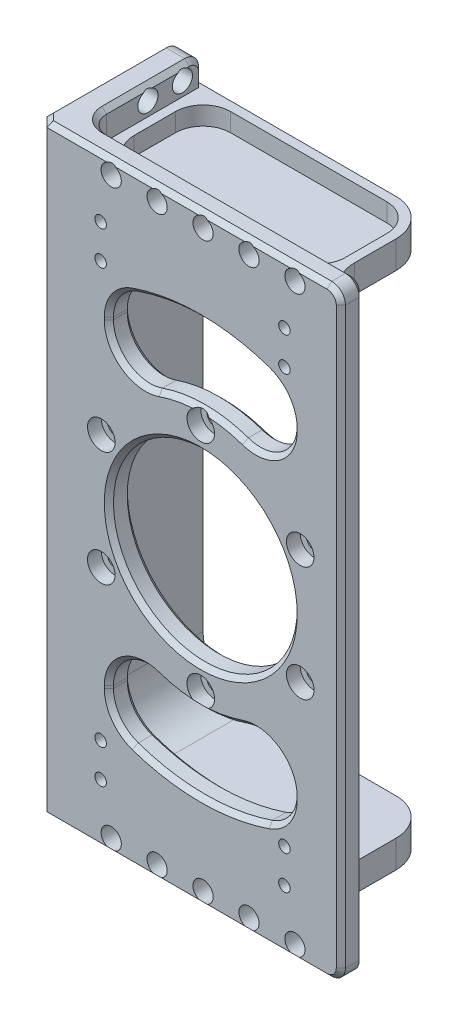
SolidWorks part; units mm, degrees
material "6061 合金"
ref_plane "前视基准面" through (0, 0, 0) normal (0, 0, 1) x (1, 0, 0)
ref_plane "上视基准面" through (0, 0, 0) normal (0, 1, 0) x (1, 0, 0)
ref_plane "右视基准面" through (0, 0, 0) normal (1, 0, 0) x (0, 0, -1)
sketch "草图1" plane through (0, 0, 0) normal (0, 0, 1) x (1, 0, 0)
  line L0 (-237.1759, 120) -> (-237.1759, 1) construction
  line L1 (-237.1759, 60.5) -> (-177.1759, 60.5) construction
  line L2 (812.8241, 60.5) -> (-387.1759, 60.5) construction
  line L3 (-165.4601, -5) -> (-232.1759, -5) construction
  line L4 (-237.1759, 126) -> (-177.1759, 126)
  line L5 (-237.1759, 126) -> (-237.1759, -5)
  line L6 (-237.1759, -5) -> (-177.1759, -5)
  line L7 (-177.1759, 126) -> (-177.1759, -5)
extrude "凸台-拉伸1" add sketch "草图1" along normal blind 5
sketch "草图2" plane through (-237.1759, 0, 0) normal (-1, 0, 0) x (0, 0, 1)
  line L0 (-235, 126) -> (-5, 126) construction
  line L1 (5, -5) -> (-25, -5)
  line L2 (5, -5) -> (5, 126)
  line L3 (5, 126) -> (-25, 126)
  line L4 (-25, -5) -> (-25, 126)
extrude "凸台-拉伸2" add sketch "草图2" along normal blind 6
sketch "草图3" plane through (0, 0, 5) normal (0, 0, 1) x (1, 0, 0)
  line L2 (-236.1759, 60.5) -> (-179.1759, 60.5) construction
  circle A2 centre (-207.6759, 60.5) radius 28.5 construction
  circle A3 centre (-207.6759, 60.5) radius 25 construction
  circle A4 centre (-207.6759, 60.5) radius 20
  dimension "D1" = 5
extrude "切除-拉伸1" cut sketch "草图3" against normal blind 10
sketch "草图4" plane through (0, 0, 5) normal (0, 0, 1) x (1, 0, 0)
  line L4 (-177.1759, 126) -> (-243.1759, 126)
  line L5 (-243.1759, 126) -> (-243.1759, -5)
  line L6 (-243.1759, -5) -> (-177.1759, -5)
  line L7 (-177.1759, -5) -> (-177.1759, 126)
  line L8 (-177.1759, 126) -> (-243.1759, 126)
  line L9 (-243.1759, 126) -> (-243.1759, -5)
  line L10 (-243.1759, -5) -> (-177.1759, -5)
  line L11 (-177.1759, -5) -> (-177.1759, 126)
  circle A0 centre (-207.6759, 60.5) radius 20 construction
  circle A1 centre (-207.6759, 60.5) radius 20
  dimension "D1" = 0
chamfer "倒角1" distance 2 angle 45 1 edges at (-243.1759, 60.5, 5)
fillet "圆角1" radius 3 4 edges at (-240.1759, 126, -25) (-177.1759, 126, 2.5) (-177.1759, -5, 2.5) (-240.1759, -5, -25)
sketch "草图5" plane through (0, 0, 5) normal (0, 0, 1) x (1, 0, 0)
  circle A0 centre (-207.6759, 60.5) radius 25 construction
  point P3 (-207.6759, 85.5)
  point P4 (-186.0252, 73)
  point P7 (-186.0252, 48)
  point P8 (-207.6759, 35.5)
  point P9 (-229.3265, 48)
  point P10 (-229.3265, 73)
  point P11 (-207.6759, 60.5)
  dimension "D1" = 6
sketch "草图13" plane through (0, 0, 5) normal (0, 0, 1) x (1, 0, 0)
  circle A0 centre (-207.6759, 85.5) radius 1.6
  circle A1 centre (-229.3265, 73) radius 1.6
  circle A2 centre (-186.0252, 73) radius 1.6
  circle A3 centre (-186.0252, 48) radius 1.6
  circle A4 centre (-207.6759, 35.5) radius 1.6
  circle A5 centre (-229.3265, 48) radius 1.6
extrude "切除-拉伸2" cut sketch "草图13" against normal blind 6
sketch "草图14" plane through (0, 0, 5) normal (0, 0, 1) x (1, 0, 0)
  circle A0 centre (-207.6759, 85.5) radius 3
  circle A1 centre (-186.0252, 73) radius 3
  circle A2 centre (-186.0252, 48) radius 3
  circle A3 centre (-207.6759, 35.5) radius 3
  circle A4 centre (-229.3265, 48) radius 3
  circle A5 centre (-229.3265, 73) radius 3
extrude "切除-拉伸3" cut sketch "草图14" against normal blind 3
chamfer "倒角4" distance 1 angle 45 12 edges at (-242.1759, -5, 4) (-210.6759, -5, 5) (-243.1759, -5, -9.5) (-178.0545, -4.1213, 5) (-243.1759, -4.1213, -24.1213) (-177.1759, 60.5, 5) (-243.1759, 60.5, -25) (-178.0545, 125.1213, 5) (-243.1759, 125.1213, -24.1213) (-210.6759, 126, 5) (-242.1759, 126, 4) (-243.1759, 126, -9.5)
sketch "草图15" plane through (0, 0, 0) normal (0, -1, 0) x (1, 0, 0)
  line L0 (-11.5, -120) -> (-5.5, -120) construction
  line L1 (-11.5, -191) -> (-11.5, -49) construction
  line L2 (-5.5, -108) -> (-5.5, -132) construction
  line L3 (-8.5, -100) -> (-8.5, -140) construction
  line L4 (-8.5, -80) -> (-8.5, -160) construction
  line L5 (-8.5, -60) -> (-8.5, -180) construction
  point P9 (-8.5, -120)
  point P13 (-8.5, -120)
  point P16 (-8.5, -120)
sketch "草图16" plane through (0, 0, 0) normal (0, 0, -1) x (-1, 0, 0)
  line L5 (237.1759, 126) -> (237.1759, 120) construction
  line L6 (237.1759, 123) -> (237.1759, -2) construction
  line L8 (237.1759, 120) -> (187.1759, 120)
  line L9 (237.1759, 120) -> (237.1759, 114)
  line L10 (237.1759, 114) -> (187.1759, 114)
  line L11 (187.1759, 120) -> (187.1759, 114)
extrude "凸台-拉伸4" add sketch "草图16" along normal up to surface (25 mm away) up to face at (-239.6759, 60.5, -25)
ref_plane "基准面1" through (0, 60.5, 0) normal (0, -1, 0) x (-1, 0, 0)
mirror "镜向1" about plane through (0, 60.5, 0) normal (0, -1, 0) of "凸台-拉伸4"
fillet "圆角3" radius 4 2 edges at (-237.1759, -2, 0) (-237.1759, 123, 0)
fillet "圆角4" radius 10 2 edges at (-237.1759, 114, -12.5) (-237.1759, 7, -12.5)
fillet "圆角5" radius 8 4 edges at (-187.1759, 117, 0) (-187.1759, 117, -25) (-187.1759, 4, 0) (-187.1759, 4, -25)
sketch "草图17" plane through (0, 120, 0) normal (0, 1, 0) x (1, 0, 0)
  line L4 (-235.1759, 4) -> (-235.1759, 2)
  line L5 (-235.1759, 2) -> (-233.1759, 2)
  line L8 (-189.1759, 8) -> (-189.1759, 17)
  line L9 (-195.1759, 23) -> (-235.1759, 23)
  line L10 (-235.1759, 23) -> (-235.1759, 4)
  line L11 (-233.1759, 2) -> (-187.1759, 2)
  line L12 (-189.1759, 8) -> (-189.1759, 17)
  line L13 (-195.1759, 23) -> (-235.1759, 23)
  line L14 (-235.1759, 23) -> (-235.1759, 4)
  line L15 (-233.1759, 2) -> (-187.1759, 2)
  arc A6 (-189.1759, 17) -> (-195.1759, 23) centre (-195.1759, 17) ccw
  arc A7 (-235.1759, 4) -> (-233.1759, 2) centre (-233.1759, 4) ccw
  arc A8 (-189.1759, 8) -> (-187.1759, 2) centre (-179.1759, 8) ccw
  arc A9 (-189.1759, 17) -> (-195.1759, 23) centre (-195.1759, 17) ccw
  arc A11 (-189.1759, 8) -> (-187.1759, 2) centre (-179.1759, 8) ccw
  dimension "D1" = 2
extrude "切除-拉伸4" cut sketch "草图17" against normal blind 4
mirror "镜向2" about plane through (0, 60.5, 0) normal (0, -1, 0) of "切除-拉伸4"
fillet "圆角6" radius 6 6 edges at (-187.1759, 118, -2) (-235.1759, 118, -23) (-235.1759, 118, -2) (-235.1759, 3, -23) (-187.1759, 3, -2) (-235.1759, 3, -2)
sketch "草图19" plane through (0, 0, 5) normal (0, 0, 1) x (1, 0, 0)
  line L0 (-243.1759, -5) -> (-237.1759, -5) construction
  line L1 (-243.1759, -5) -> (-177.1759, -5) construction
  line L2 (-237.1759, -5) -> (-177.1759, -5) construction
  line L3 (-207.1759, -5) -> (-207.1759, 1) construction
  line L4 (-217.1759, -2) -> (-197.1759, -2)
  line L5 (-227.1759, -2) -> (-187.1759, -2)
  circle A0 centre (-227.1759, -2) radius 2.2
  circle A1 centre (-217.1759, -2) radius 2.2
  circle A2 centre (-207.1759, -2) radius 2.2
  circle A3 centre (-197.1759, -2) radius 2.2
  circle A4 centre (-187.1759, -2) radius 2.2
  point P13 (-207.1759, -2)
  point P15 (-207.1759, -2)
extrude "切除-拉伸5" cut sketch "草图19" against normal blind 18
mirror "镜向3" about plane through (0, 60.5, 0) normal (0, -1, 0) of "切除-拉伸5"
sketch "草图20" plane through (-243.1759, 0, 0) normal (-1, 0, 0) x (0, 0, 1)
  line L0 (5, -5) -> (-1, -5) construction
  line L1 (5, -5) -> (5, 126) construction
  line L2 (4, -5) -> (2.5858, -5) construction
  line L3 (-1, -5) -> (-25, -5) construction
  line L4 (-5, -5) -> (-235, -5) construction
  line L5 (-13, -5) -> (-13, 1) construction
  line L6 (-20.5, -2) -> (-5.5, -2) construction
  circle A0 centre (-20.5, -2) radius 2.2
  circle A1 centre (-13, -2) radius 2.2
  point P15 (-13, -2)
extrude "切除-拉伸6" cut sketch "草图20" against normal blind 18
mirror "镜向4" about plane through (0, 60.5, 0) normal (0, -1, 0) of "切除-拉伸6"
sketch "草图21" plane through (0, 0, 5) normal (0, 0, 1) x (1, 0, 0)
  line L0 (-207.6759, 60.5) -> (-209.4659, 60.5)
  line L1 (-14.3, 60.5) -> (14.3, 60.5) construction
  line L2 (-209.4659, 60.5) -> (-209.4659, 64.19)
  line L4 (-229.4659, 113.065) -> (-189.4659, 113.065)
  line L5 (-229.4659, 113.065) -> (-229.4659, 15.315)
  line L6 (-229.4659, 15.315) -> (-189.4659, 15.315)
  line L7 (-189.4659, 113.065) -> (-189.4659, 15.315)
  line L8 (-229.4659, 113.065) -> (-189.4659, 15.315) construction
  line L9 (-229.4659, 15.315) -> (-189.4659, 113.065) construction
hole_wizard "M3 螺纹孔1" positions "草图22" profile "草图23" tap size "M3" standard "GB"
sketch "草图22" plane through (0, 0, 5) normal (0, 0, 1) x (1, 0, 0)
  point P0 (-229.4659, 113.065)
  point P3 (-189.4659, 113.065)
  point P6 (-189.4659, 15.315)
  point P9 (-229.4659, 15.315)
sketch "草图23" plane through (-229.4659, 113.065, 5) normal (1, 0, 0) x (0, -1, 0)
  line L0 (0, 0) -> (0, 8.2511)
  line L1 (0, 8.2511) -> (1.25, 7.5)
  line L2 (1.25, 7.5) -> (1.25, 0)
  line L5 (1.25, 0) -> (0, 0)
  line L10 (0, 8.2511) -> (-1.25, 7.5) construction
  line L11 (0, -6.35) -> (0, 107.95) construction
  dimension "螺纹孔钻头直径" = 2.5
  dimension "螺纹孔钻头深度" = 7.5
  dimension "导头角度" = 118
cosmetic thread "孔螺蚊线1" parameters "D1"=6, "D2"=3
cosmetic thread "孔螺蚊线2" parameters "D1"=6, "D2"=3
cosmetic thread "孔螺蚊线3" parameters "D1"=6, "D2"=3
cosmetic thread "孔螺蚊线4" parameters "D1"=6, "D2"=3
mirror "镜向5" about plane through (0, 60.5, 0) normal (0, -1, 0) of "M3 螺纹孔1"
cosmetic thread "孔螺蚊线5" parameters "D1"=6, "D2"=3
cosmetic thread "孔螺蚊线6" parameters "D1"=6, "D2"=3
cosmetic thread "孔螺蚊线7" parameters "D1"=6, "D2"=3
cosmetic thread "孔螺蚊线8" parameters "D1"=6, "D2"=3
sketch "草图24" plane through (-243.1759, 0, 0) normal (-1, 0, 0) x (0, 0, 1)
  line L0 (5, 60.5) -> (-7.12, 60.5)
  line L3 (-14.3, 60.5) -> (14.3, 60.5) construction
  line L4 (-7.12, 60.5) -> (-7.12, 35.2)
  line L5 (-7.12, 60.5) -> (-7.12, 85.8)
hole_wizard "M3 螺纹孔2" positions "草图25" profile "草图26" tap size "M3" standard "GB"
sketch "草图25" plane through (-243.1759, 0, 0) normal (-1, 0, 0) x (0, 0, 1)
  point P0 (-7.12, 85.8)
  point P3 (-7.12, 35.2)
sketch "草图26" plane through (-243.1759, 85.8, -7.12) normal (0, 1, 0) x (0, 0, 1)
  line L0 (0, 0) -> (0, 8.2511)
  line L1 (0, 8.2511) -> (1.25, 7.5)
  line L2 (1.25, 7.5) -> (1.25, 0)
  line L5 (1.25, 0) -> (0, 0)
  line L10 (0, 8.2511) -> (-1.25, 7.5) construction
  line L11 (0, -6.35) -> (0, 107.95) construction
  dimension "螺纹孔钻头直径" = 2.5
  dimension "螺纹孔钻头深度" = 7.5
  dimension "导头角度" = 118
cosmetic thread "孔螺蚊线9" parameters "D1"=6, "D2"=3
cosmetic thread "孔螺蚊线10" parameters "D1"=6, "D2"=3
sketch "草图27" plane through (0, 0, 0) normal (0, 0, -1) x (-1, 0, 0)
  line L0 (207.6759, 105.5) -> (207.6759, 89) construction
  line L1 (187.6759, 100.8113) -> (187.6759, 80.8039)
  line L2 (227.6759, 100.8113) -> (227.6759, 80.8039)
  line L3 (227.6759, 60.5) -> (227.6759, -966.5522) construction
  line L4 (207.6759, 60.5) -> (207.6759, -966.5522) construction
  line L5 (187.6759, 60.5) -> (187.6759, -966.5522) construction
  line L6 (187.6759, 40.1961) -> (187.6759, 20.1887)
  line L7 (207.6759, 32) -> (207.6759, 15.5) construction
  line L8 (227.6759, 40.1961) -> (227.6759, 20.1887)
  arc A0 (187.6759, 40.1961) -> (227.6759, 40.1961) centre (207.6759, 60.5) ccw
  arc A1 (187.6759, 20.1887) -> (227.6759, 20.1887) centre (207.6759, 60.5) ccw
  arc A2 (227.6759, 80.8039) -> (187.6759, 80.8039) centre (207.6759, 60.5) ccw
  arc A3 (227.6759, 100.8113) -> (187.6759, 100.8113) centre (207.6759, 60.5) ccw
  dimension "D1" = 20
  dimension "D2" = 20
extrude "切除-拉伸7" cut sketch "草图27" against normal blind 10
fillet "圆角7" radius 8 8 edges at (-187.6759, 20.1887, 2.5) (-227.6759, 40.1961, 2.5) (-227.6759, 20.1887, 2.5) (-187.6759, 40.1961, 2.5) (-187.6759, 80.8039, 2.5) (-227.6759, 100.8113, 2.5) (-227.6759, 80.8039, 2.5) (-187.6759, 100.8113, 2.5)
chamfer "倒角5" distance 1 angle 45 34 edges at (-187.6759, 60.5, 0) (-187.6759, 60.5, 5) (-207.6759, 105.5, 0) (-189.166, 100.1499, 0) (-226.1857, 100.1499, 0) (-187.6759, 95.2355, 0) (-227.6759, 95.2355, 0) (-191.0413, 88.4502, 0) (-224.3105, 88.4502, 0) (-207.6759, 89, 0) (-207.6759, 89, 5) (-191.0413, 88.4502, 5) (-224.3105, 88.4502, 5) (-187.6759, 95.2355, 5) (-227.6759, 95.2355, 5) (-189.166, 100.1499, 5) (-226.1857, 100.1499, 5) (-207.6759, 105.5, 5) (-207.6759, 32, 0) (-191.0413, 32.5498, 0) (-224.3105, 32.5498, 0) (-187.6759, 25.7645, 0) (-227.6759, 25.7645, 0) (-189.166, 20.8501, 0) (-226.1857, 20.8501, 0) (-207.6759, 15.5, 0) (-207.6759, 32, 5) (-224.3105, 32.5498, 5) (-191.0413, 32.5498, 5) (-227.6759, 25.7645, 5) (-187.6759, 25.7645, 5) (-226.1857, 20.8501, 5) (-189.166, 20.8501, 5) (-207.6759, 15.5, 5)
chamfer "倒角6" distance 1 angle 45 13 edges at (-237.1759, -0.5, -25) (-237.1759, 121.5, -25) (-237.1759, -4.1213, -24.1213) (-237.1759, 125.1213, -24.1213) (-237.1759, -5, -13) (-237.1759, 126, -13) (-236.0043, -5, -1.1716) (-236.0043, 126, -1.1716) (-206.6759, -5, 0) (-206.6759, 126, 0) (-178.0545, -4.1213, 0) (-178.0545, 125.1213, 0) (-177.1759, 60.5, 0)
